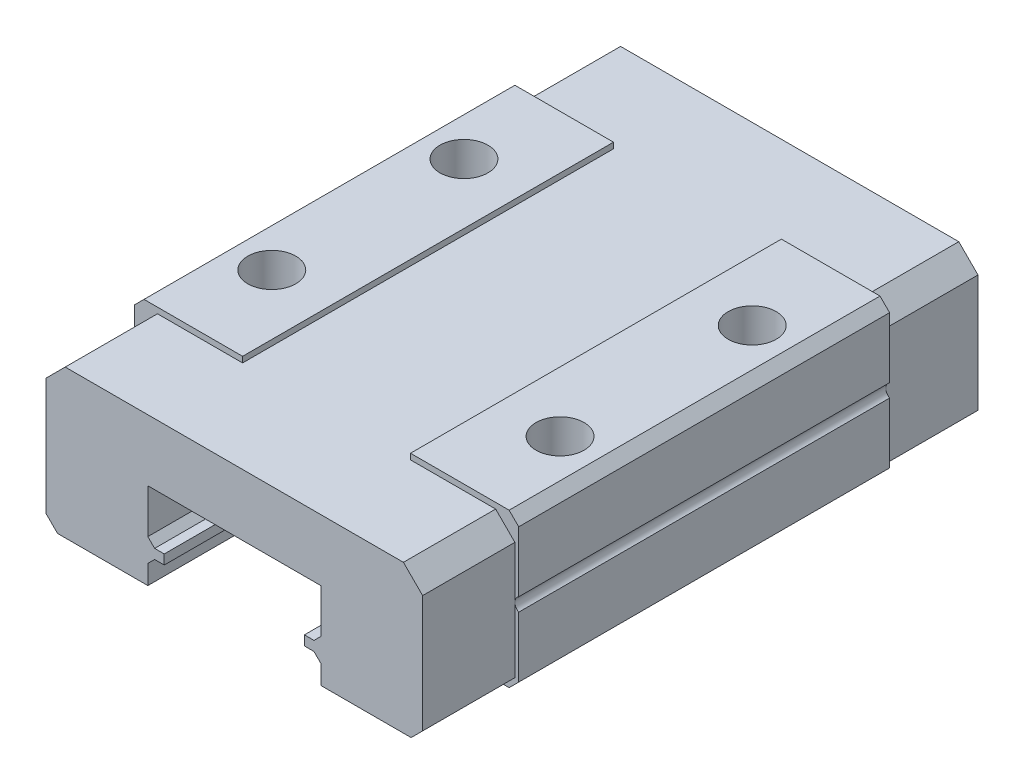
SolidWorks part; units mm, degrees
material "AISI 1020 钢，冷轧"
ref_plane "前视基准面" through (0, 0, 0) normal (0, 0, 1) x (1, 0, 0)
ref_plane "上视基准面" through (0, 0, 0) normal (0, 1, 0) x (1, 0, 0)
ref_plane "右视基准面" through (0, 0, 0) normal (1, 0, 0) x (0, 0, -1)
sketch "草图1" plane through (0, 0, 0) normal (0, 0, 1) x (1, 0, 0)
  line L0 (0, 0) -> (0, 18.7331) construction
  line L1 (-10, 0) -> (-10, 8)
  line L2 (4.5, 0) -> (4.5, 1)
  line L3 (4.5, 1) -> (4.1464, 1.3536)
  line L4 (4.1464, 1.3536) -> (3.6464, 1.3536)
  line L5 (3.6464, 1.3536) -> (3.6464, 1.8536)
  line L6 (3.6464, 1.8536) -> (4.1464, 1.8536)
  line L7 (4.1464, 1.8536) -> (4.5, 2.2071)
  line L8 (4.5, 2.2071) -> (4.5, 4.5)
  line L9 (4.5, 4.5) -> (-4.5, 4.5)
  line L10 (4.5, 0) -> (10, 0)
  line L11 (10, 0) -> (10, 8)
  line L12 (10, 8) -> (-10, 8)
  line L13 (-4.5, 0) -> (-10, 0)
  line L14 (-4.5, 2.2071) -> (-4.5, 4.5)
  line L15 (-4.1464, 1.8536) -> (-4.5, 2.2071)
  line L16 (-3.6464, 1.8536) -> (-4.1464, 1.8536)
  line L17 (-3.6464, 1.3536) -> (-3.6464, 1.8536)
  line L18 (-4.1464, 1.3536) -> (-3.6464, 1.3536)
  line L19 (-4.5, 1) -> (-4.1464, 1.3536)
  line L20 (-4.5, 0) -> (-4.5, 1)
  point P16 (0, 8)
  point P19 (0, 4.5)
  dimension "D1" = 4.5
  dimension "D2" = 1
  dimension "D3" = 0.5
  dimension "D4" = 0.5
  dimension "D5" = 0.5
  dimension "D6" = 4.5
  dimension "D7" = 10
  dimension "D8" = 8
extrude "凸台-拉伸1" add sketch "草图1" against normal blind 28.9
sketch "草图2" plane through (0, 8, 0) normal (0, 1, 0) x (1, 0, 0)
  line L0 (0, 28.9) -> (0, 0) construction
  line L1 (10, 28.9) -> (-10, 28.9) construction
  line L2 (10, 14.45) -> (-10, 14.45) construction
  line L3 (10, 28.9) -> (10, 0) construction
  line L4 (-10, 28.9) -> (-10, 0) construction
hole_wizard "M3 螺纹孔1" positions "草图4" profile "草图3" tap size "M3" standard "Gb"
sketch "草图4" plane through (0, 8, 0) normal (0, 1, 0) x (1, 0, 0)
  line L0 (0, 28.9) -> (0, 0) construction
  line L1 (10, 14.45) -> (-10, 14.45) construction
  point P0 (7.5, 19.45)
  dimension "D1" = 7.5
  dimension "D2" = 5
sketch "草图3" plane through (7.5, 8, -19.45) normal (1, 0, 0) x (0, 0, 1)
  line L0 (0, 0) -> (0, 3.7511)
  line L1 (0, 3.7511) -> (1.25, 3)
  line L2 (1.25, 3) -> (1.25, 0)
  line L5 (1.25, 0) -> (0, 0)
  line L10 (0, 3.7511) -> (-1.25, 3) construction
  line L11 (0, -6.35) -> (0, 107.95) construction
  dimension "螺纹孔钻头直径" = 2.5
  dimension "螺纹孔钻头深度" = 3
  dimension "导头角度" = 118
cosmetic thread "孔螺蚊线1" parameters "D1"=3, "D2"=3
ref_plane "基准面1" through (0, 0, -14.45) normal (0, 0, -1) x (-1, 0, 0)
ref_plane "基准面2" through (0, 0, 0) normal (-1, 0, 0) x (0, 0, 1)
mirror "镜向1" about plane through (0, 0, -14.45) normal (0, 0, -1) of "M3 螺纹孔1"
mirror "镜向2" about plane through (0, 0, 0) normal (-1, 0, 0) of "镜向1"
chamfer "倒角1" distance 0.5 angle 45 2 edges at (10, 8, -14.45) (-10, 8, -14.45)
sketch "草图5" plane through (0, 8, 0) normal (0, 1, 0) x (1, 0, 0)
  line L0 (-9.5, 24.1) -> (-4.3686, 24.1)
  line L1 (-9.5, 28.9) -> (-9.5, 0) construction
  line L2 (-4.3686, 24.1) -> (-4.3686, 4.8)
  line L3 (-4.3686, 4.8) -> (-9.5, 4.8)
  line L4 (0, 28.9) -> (0, -1.0585) construction
  line L5 (9.5, 28.9) -> (-9.5, 28.9) construction
  line L6 (4.3686, 4.8) -> (9.5, 4.8)
  line L7 (4.3686, 24.1) -> (4.3686, 4.8)
  line L8 (9.5, 24.1) -> (4.3686, 24.1)
  line L9 (9.5, 0) -> (-9.5, 0) construction
  line L10 (-9.5, 24.1) -> (-10, 24.1)
  line L11 (-10, 0) -> (-10, 28.9) construction
  line L12 (-10, 24.1) -> (-10, 28.9)
  line L13 (-10, 28.9) -> (10, 28.9)
  line L14 (10, 28.9) -> (10, 24.1)
  line L15 (10, 28.9) -> (10, 0) construction
  line L16 (10, 24.1) -> (9.5, 24.1)
  line L17 (9.5, 4.8) -> (10, 4.8)
  line L18 (10, 4.8) -> (10, 0)
  line L19 (10, 0) -> (-10, 0)
  line L20 (-10, 0) -> (-10, 4.8)
  line L21 (-10, 4.8) -> (-9.5, 4.8)
  dimension "D1" = 4.8
  dimension "D2" = 4.8
extrude "切除-拉伸1" cut sketch "草图5" against normal blind 0.3
sketch "草图6" plane through (0, 7.7, 0) normal (0, 1, 0) x (1, 0, 0)
  line L0 (-10, 28.9) -> (-9.8, 28.9)
  line L1 (9.8, 28.9) -> (-9.8, 28.9) construction
  line L2 (-9.8, 28.9) -> (-9.8, 24.1)
  line L3 (-9.8, 24.1) -> (-10, 24.1)
  line L4 (-10, 0) -> (-10, 28.9) construction
  line L5 (-10, 24.1) -> (-10, 28.9)
  line L6 (0, 28.9) -> (0, 0) construction
  line L7 (-10, 14.45) -> (10, 14.45) construction
  line L8 (10, 28.9) -> (10, 0) construction
  line L9 (10, 24.1) -> (10, 28.9)
  line L10 (9.8, 24.1) -> (10, 24.1)
  line L11 (9.8, 28.9) -> (9.8, 24.1)
  line L12 (10, 28.9) -> (9.8, 28.9)
  line L13 (10, 0) -> (9.8, 0)
  line L14 (9.8, 0) -> (9.8, 4.8)
  line L15 (9.8, 4.8) -> (10, 4.8)
  line L16 (10, 4.8) -> (10, 0)
  line L17 (-10, 4.8) -> (-10, 0)
  line L18 (-9.8, 4.8) -> (-10, 4.8)
  line L19 (-9.8, 0) -> (-9.8, 4.8)
  line L20 (-10, 0) -> (-9.8, 0)
extrude "切除-拉伸2" cut sketch "草图6" against normal blind 8.3
chamfer "倒角2" distance 1 angle 45 4 edges at (-9.8, 7.7, -26.5) (9.8, 7.7, -26.5) (9.8, 7.7, -2.4) (-9.8, 7.7, -2.4)
chamfer "倒角3" distance 0.6 angle 45 4 edges at (9.8, 0, -2.4) (-9.8, 0, -2.4) (-9.8, 0, -26.5) (9.8, 0, -26.5)
chamfer "倒角4" distance 0.5 angle 45 2 edges at (10, 0, -14.45) (-10, 0, -14.45)
sketch "草图7" plane through (0, 0, -24.1) normal (0, 0, -1) x (-1, 0, 0)
  line L0 (-9.8, 0.6) -> (-9.8, 6.7) construction
  line L1 (-4.5, 0) -> (-9.2, 0) construction
  circle A0 centre (-10.2, 4) radius 0.4
  dimension "D1" = 0.8
  dimension "D2" = 0.4
  dimension "D3" = 4
extrude "切除-拉伸3" cut sketch "草图7" against normal up to surface (19.3 mm away) up to face at (8.6488, 4.9455, -4.8)
